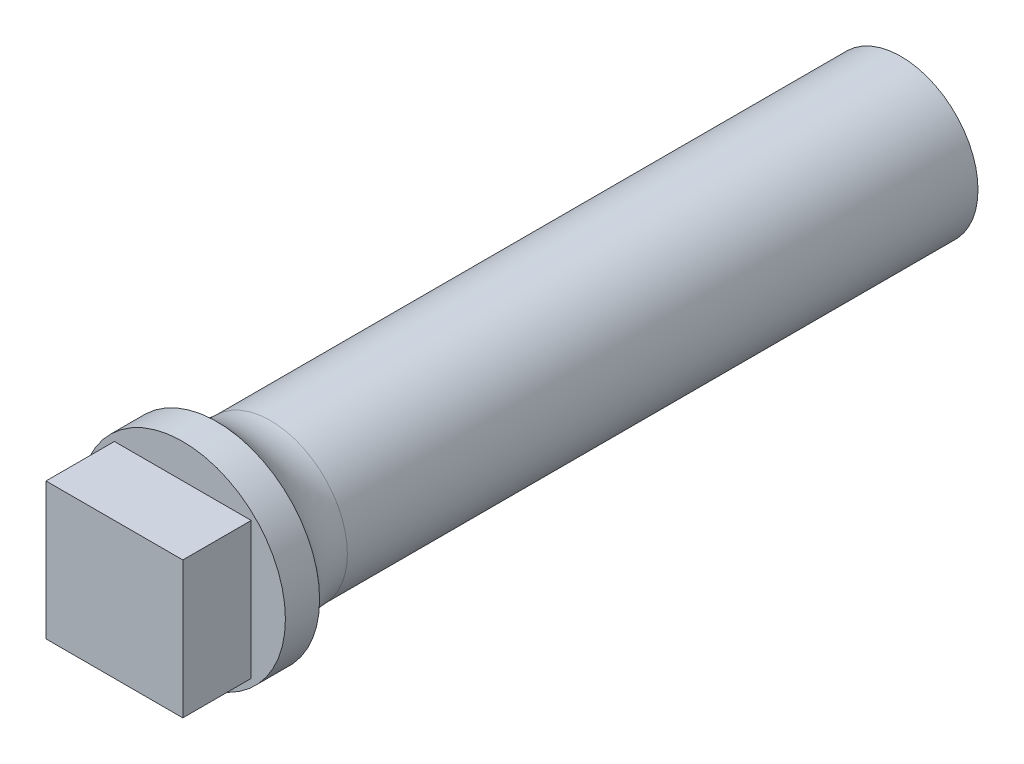
SolidWorks part; units mm, degrees
ref_plane "Front Plane" through (0, 0, 0) normal (0, 0, 1) x (1, 0, 0)
ref_plane "Top Plane" through (0, 0, 0) normal (0, 1, 0) x (1, 0, 0)
ref_plane "Right Plane" through (0, 0, 0) normal (1, 0, 0) x (0, 0, -1)
sketch "草图1" plane through (0, 0, 0) normal (0, 0, 1) x (1, 0, 0)
  circle A0 centre (0, 0) radius 2.25
  dimension "D1" = 4.5
extrude "凸台-拉伸2" add sketch "草图1" along normal blind 20
sketch "草图7" plane through (0, 0, 0) normal (0, 0, 1) x (1, 0, 0)
  line L1 (1.2, -1.2) -> (-1.2, -1.2)
  line L2 (1.2, -1.2) -> (1.2, 1.2)
  line L3 (1.2, 1.2) -> (-1.2, 1.2)
  line L4 (-1.2, -1.2) -> (-1.2, 1.2)
  line L5 (1.2, -1.2) -> (-1.2, 1.2) construction
  line L6 (1.2, 1.2) -> (-1.2, -1.2) construction
  point P0 (0, 0)
  dimension "D1" = 2.4
  dimension "D2" = 2.4
extrude "切除-拉伸3" cut sketch "草图7" along normal blind 2.5 from surface starting at face at (2.25, 0, 0)
sketch "草图9" plane through (0, 0, 20) normal (0, 0, 1) x (1, 0, 0)
  circle A0 centre (0, 0) radius 3
extrude "凸台-拉伸4" add sketch "草图9" along normal blind 1
sketch "草图10" plane through (0, 0, 21) normal (0, 0, 1) x (1, 0, 0)
  line L1 (2, -2) -> (-2, -2)
  line L2 (2, -2) -> (2, 2)
  line L3 (2, 2) -> (-2, 2)
  line L4 (-2, -2) -> (-2, 2)
  line L5 (2, -2) -> (-2, 2) construction
  line L6 (2, 2) -> (-2, -2) construction
  point P0 (0, 0)
  dimension "D1" = 4
  dimension "D2" = 4
extrude "凸台-拉伸5" add sketch "草图10" along normal blind 2
sketch "草图12" plane through (0, 0, 0) normal (0, 0, -1) x (-1, 0, 0)
  circle A0 centre (0, 0) radius 1
fillet "圆角1" radius 2 1 edges at (2.25, 0, 20)
